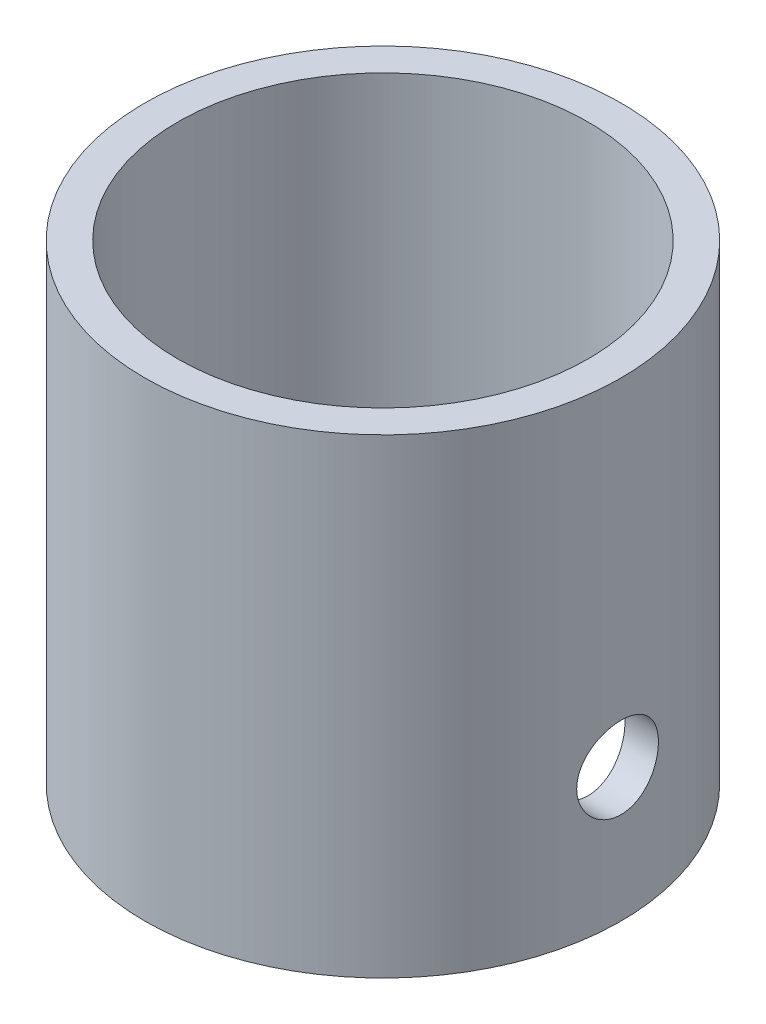
SolidWorks part; units mm, degrees
ref_plane "Front Plane" through (0, 0, 0) normal (0, 0, 1) x (1, 0, 0)
ref_plane "Top Plane" through (0, 0, 0) normal (0, 1, 0) x (1, 0, 0)
ref_plane "Right Plane" through (0, 0, 0) normal (1, 0, 0) x (0, 0, -1)
sketch "Sketch2" plane through (0, 0, 0) normal (0, 1, 0) x (1, 0, 0)
  circle A0 centre (0, 0) radius 20.25
  circle A1 centre (0, 0) radius 17.4512
  dimension "D1" = 40.5
extrude "Boss-Extrude1" add sketch "Sketch2" along normal blind 40
sketch "Sketch5" plane through (0, 0, 0) normal (1, 0, 0) x (0, 0, -1)
  circle A0 centre (0, 11.317) radius 3.475
  dimension "D1" = 6.95
extrude "Cut-Extrude1" cut sketch "Sketch5" against normal blind 40 and the other way blind 40
